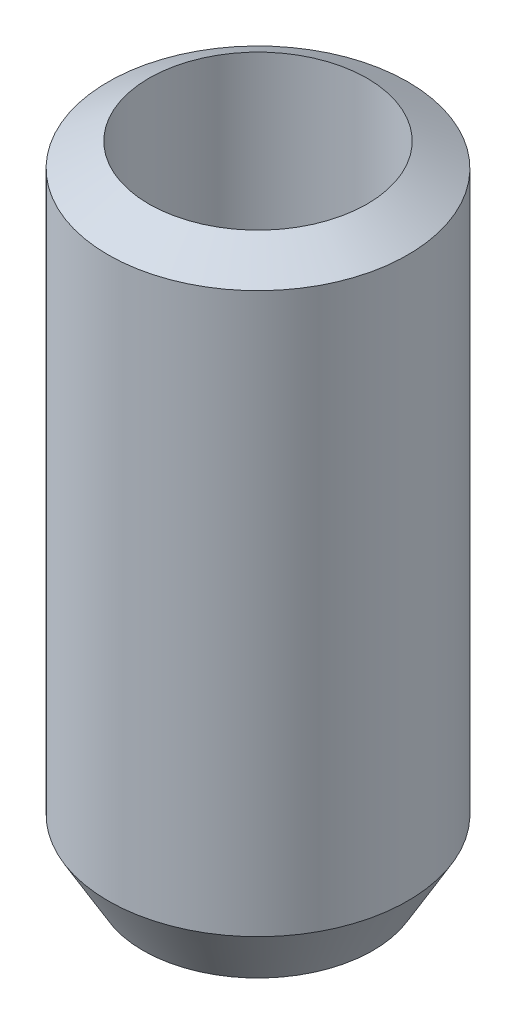
SolidWorks part; units mm, degrees
ref_plane "Front Plane" through (0, 0, 0) normal (0, 0, 1) x (1, 0, 0)
ref_plane "Top Plane" through (0, 0, 0) normal (0, 1, 0) x (1, 0, 0)
ref_plane "Right Plane" through (0, 0, 0) normal (1, 0, 0) x (0, 0, -1)
sketch "Sketch1" plane through (0, 0, 0) normal (0, 1, 0) x (1, 0, 0)
  circle A0 centre (0, 0) radius 20
  dimension "SHAFT_OD" = 40
extrude "Boss-Extrude1" add sketch "Sketch1" along normal blind 87.3976
sketch "Sketch2" plane through (0, 0, 0) normal (0, 1, 0) x (1, 0, 0)
  circle A0 centre (0, 0) radius 14.5548
  dimension "BORE_D" = 29.1096
extrude "Cut-Extrude1" cut sketch "Sketch2" along normal through all
chamfer "Chamfer1" distance 4.6611 angle 60 2 edges at (0, 87.3976, 20) (0, 0, 20) first distance on face at (0, 87.3976, 20) first distance on face at (0, 0, 14.5548)
